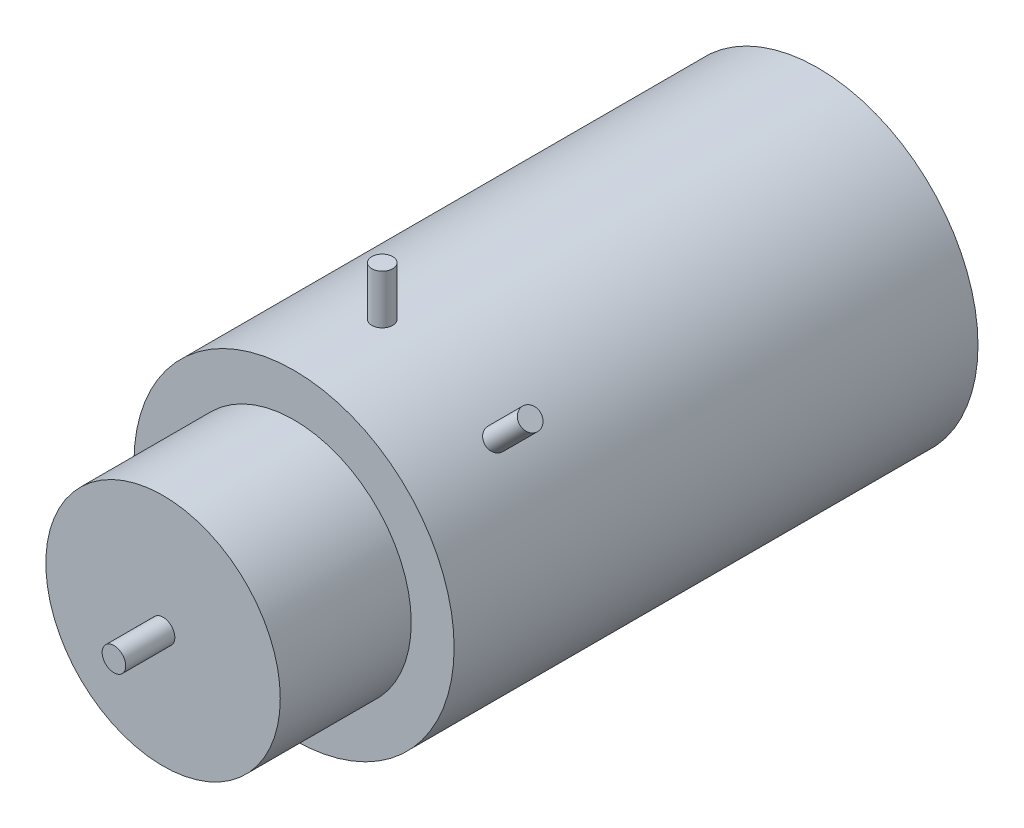
SolidWorks part; units mm, degrees
ref_plane "Front Plane" through (0, 0, 0) normal (0, 0, 1) x (1, 0, 0)
ref_plane "Top Plane" through (0, 0, 0) normal (0, 1, 0) x (1, 0, 0)
ref_plane "Right Plane" through (0, 0, 0) normal (1, 0, 0) x (0, 0, -1)
sketch "Sketch1" plane through (0, 0, 0) normal (0, 0, 1) x (1, 0, 0)
  circle A0 centre (0, 0) radius 31.0515
  dimension "D1" = 62.103
extrude "Boss-Extrude1" add sketch "Sketch1" along normal blind 101.6
sketch "Sketch2" plane through (0, 0, 101.6) normal (0, 0, 1) x (1, 0, 0)
  circle A0 centre (0, 0) radius 22.733
  dimension "D1" = 45.466
extrude "Boss-Extrude2" add sketch "Sketch2" along normal blind 25.4
sketch "Sketch3" plane through (0, 0, 127) normal (0, 0, 1) x (1, 0, 0)
  circle A0 centre (0, 0) radius 2.286
  dimension "D1" = 4.572
extrude "Boss-Extrude3" add sketch "Sketch3" along normal blind 9.525
ref_plane "Plane1" through (0, 31.0515, 0) normal (0, 1, 0) x (1, 0, 0)
sketch "Sketch4" plane through (0, 31.0515, 0) normal (0, 1, 0) x (1, 0, 0)
  circle A0 centre (0, -84.4874) radius 2.032
  dimension "D1" = 4.064
extrude "Boss-Extrude4" add sketch "Sketch4" along normal blind 9.525 separate body
ref_axis "Axis1" through (0, 0, 143.3513) along (0, 0, -1)
pattern_circular "CirPattern3" count 2 every 45 about axis through (0, 0, 143.3513) along (0, 0, -1) of bodies 104
